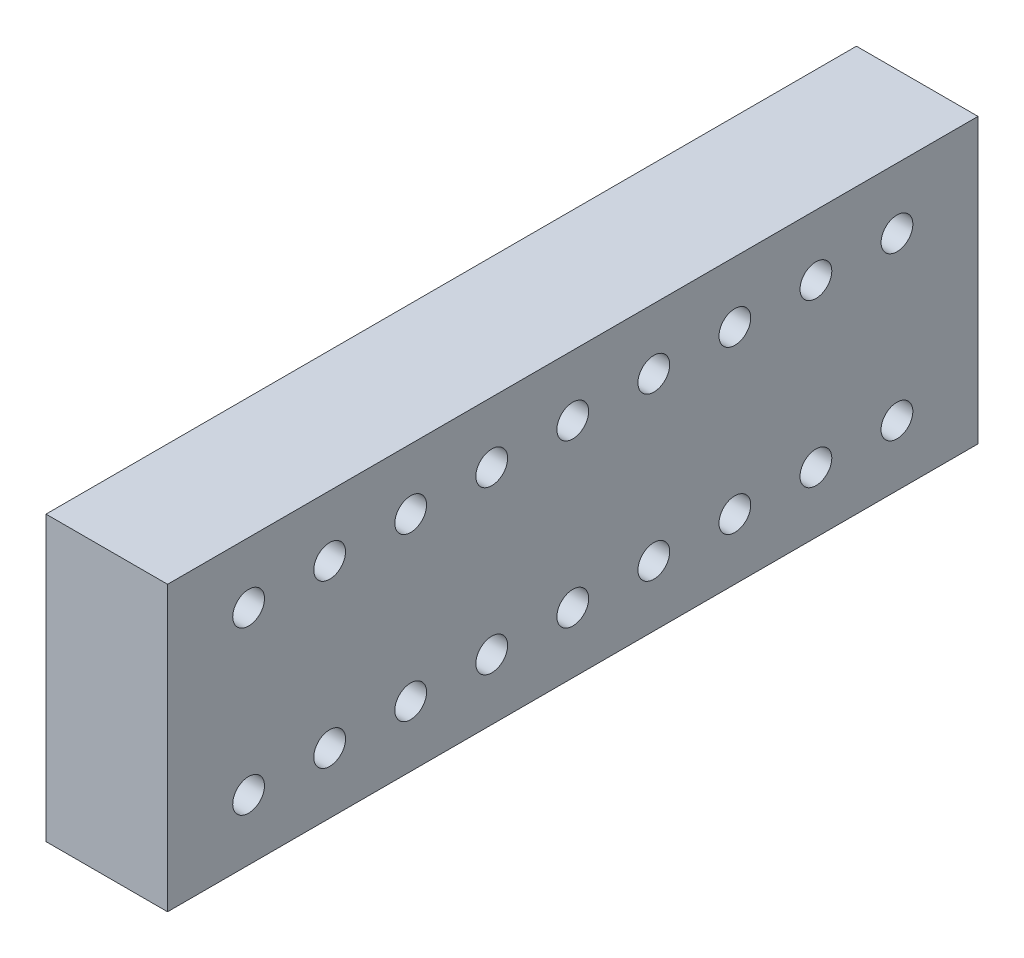
SolidWorks part; units mm, degrees
ref_plane "Front Plane" through (0, 0, 0) normal (0, 0, 1) x (1, 0, 0)
ref_plane "Top Plane" through (0, 0, 0) normal (0, 1, 0) x (1, 0, 0)
ref_plane "Right Plane" through (0, 0, 0) normal (1, 0, 0) x (0, 0, -1)
sketch "Sketch1" plane through (0, 0, 0) normal (0, 0, 1) x (1, 0, 0)
  line L1 (0, 0) -> (19.05, 0)
  line L2 (0, 0) -> (0, 44.45)
  line L3 (0, 44.45) -> (19.05, 44.45)
  line L4 (19.05, 0) -> (19.05, 44.45)
  dimension "D1" = 44.45
  dimension "D2" = 19.05
extrude "Boss-Extrude1" add sketch "Sketch1" along normal blind 127
sketch "Sketch2" plane through (19.05, 0, 0) normal (1, 0, 0) x (0, 0, -1)
  line L0 (-127, 0) -> (0, 0) construction
  line L1 (-127, 0) -> (-127, 44.45) construction
  circle A0 centre (-114.3, 9.525) radius 2.4892
  circle A1 centre (-101.6, 9.525) radius 2.4892
  circle A2 centre (-88.9, 9.525) radius 2.4892
  circle A3 centre (-114.3, 34.925) radius 2.4892
  circle A4 centre (-101.6, 34.925) radius 2.4892
  circle A5 centre (-88.9, 34.925) radius 2.4892
  circle A6 centre (-76.2, 9.525) radius 2.4892
  circle A7 centre (-63.5, 9.525) radius 2.4892
  circle A8 centre (-50.8, 9.525) radius 2.4892
  circle A9 centre (-38.1, 9.525) radius 2.4892
  circle A10 centre (-25.4, 9.525) radius 2.4892
  circle A11 centre (-12.7, 9.525) radius 2.4892
  circle A12 centre (-76.2, 34.925) radius 2.4892
  circle A13 centre (-63.5, 34.925) radius 2.4892
  circle A14 centre (-50.8, 34.925) radius 2.4892
  circle A15 centre (-38.1, 34.925) radius 2.4892
  circle A16 centre (-25.4, 34.925) radius 2.4892
  circle A17 centre (-12.7, 34.925) radius 2.4892
  dimension "D1" = 4.9784
  dimension "D2" = 9.525
  dimension "D3" = 12.7
  dimension "D4" = 9
  dimension "D5" = 2
extrude "Cut-Extrude1" cut sketch "Sketch2" against normal through all
